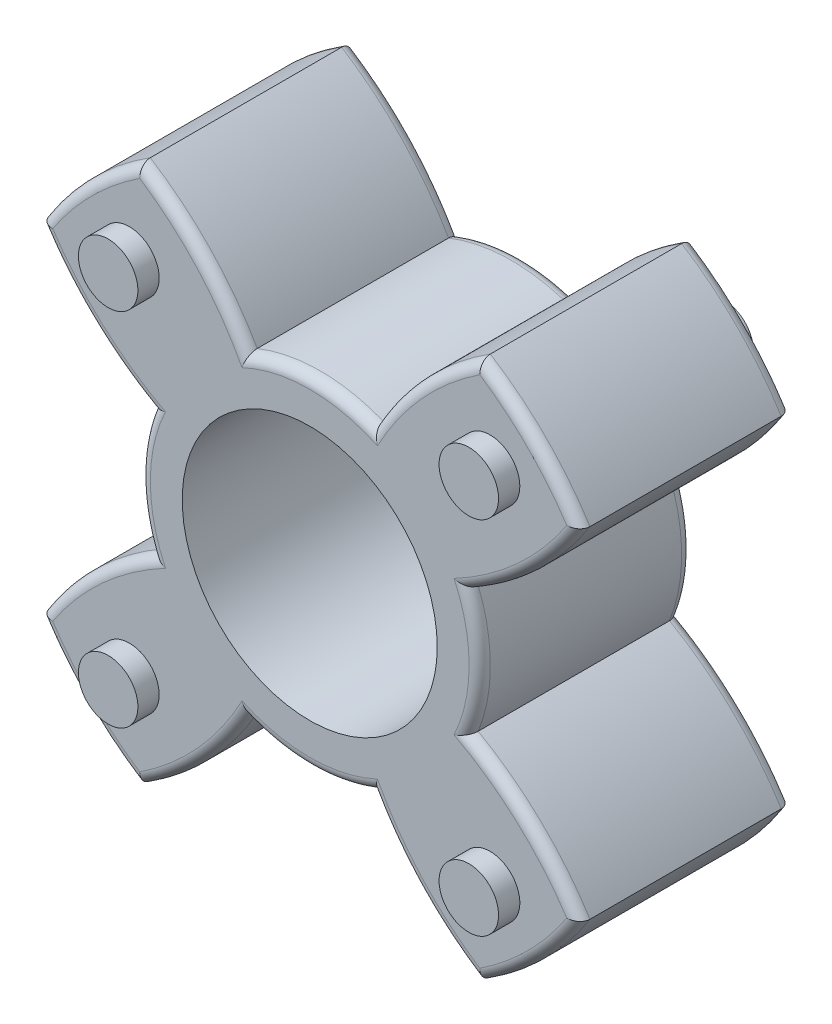
SolidWorks part; units mm, degrees
ref_plane "Front Plane" through (0, 0, 0) normal (0, 0, 1) x (1, 0, 0)
ref_plane "Top Plane" through (0, 0, 0) normal (0, 1, 0) x (1, 0, 0)
ref_plane "Right Plane" through (0, 0, 0) normal (1, 0, 0) x (0, 0, -1)
sketch "Sketch1" plane through (0, 0, 0) normal (0, 0, 1) x (1, 0, 0)
  arc A0 (8, 12.6886) -> (2.9688, 7.4288) centre (16, 0) ccw
  arc A1 (-8, -12.6886) -> (-2.9688, -7.4288) centre (-16, 0) ccw
  arc A2 (-12.6886, 8) -> (-7.4288, 2.9688) centre (0, 16) ccw
  arc A3 (12.6886, -8) -> (7.4288, -2.9688) centre (0, -16) ccw
  arc A4 (12.6886, 8) -> (8, 12.6886) centre (0, 0) ccw
  arc A5 (-8, 12.6886) -> (-12.6886, 8) centre (0, 0) ccw
  arc A6 (-12.6886, -8) -> (-8, -12.6886) centre (0, 0) ccw
  arc A7 (8, -12.6886) -> (12.6886, -8) centre (0, 0) ccw
  arc A8 (-7.4288, 2.9688) -> (-7.4288, -2.9688) centre (0, 0) ccw
  circle A9 centre (0, 0) radius 6
  arc A10 (7.4288, 2.9688) -> (12.6886, 8) centre (0, 16) ccw
  arc A11 (-2.9688, 7.4288) -> (-8, 12.6886) centre (-16, 0) ccw
  arc A12 (2.9688, 7.4288) -> (-2.9688, 7.4288) centre (0, 0) ccw
  arc A13 (-2.9688, -7.4288) -> (2.9687, -7.4288) centre (0, 0) ccw
  arc A14 (2.9687, -7.4288) -> (8, -12.6886) centre (16, 0) ccw
  arc A15 (7.4288, -2.9688) -> (7.4288, 2.9688) centre (0, 0) ccw
  arc A16 (-7.4288, -2.9688) -> (-12.6886, -8) centre (0, -16) ccw
extrude "Boss-Extrude1" add sketch "Sketch1" along normal blind 10
sketch "Sketch2" plane through (0, 0, 10) normal (0, 0, 1) x (1, 0, 0)
  circle A1 centre (-8.4853, 8.4853) radius 1.4
extrude "Boss-Extrude2" add sketch "Sketch2" along normal blind 1
ref_axis "Axis1" through (0, 0, 0) along (0, 0, 1)
pattern_circular "CirPattern1" count 4 over 360 about axis through (0, 0, 0) along (0, 0, 1) of "Boss-Extrude2"
sketch "Sketch3" plane through (0, 0, 0) normal (0, 0, -1) x (-1, 0, 0)
  circle A0 centre (-8.4853, 8.4853) radius 1.4
extrude "Boss-Extrude3" add sketch "Sketch3" along normal blind 1
pattern_circular "CirPattern2" count 2 over 360 about axis through (0, 0, 0) along (0, 0, 1) of "Boss-Extrude3"
fillet "Fillet1" radius 0.5 16 edges at (5.1605, -10.3685, 0) (0, -8, 0) (-5.1605, -10.3685, 0) (-10.6066, -10.6066, 0) (-10.3685, -5.1605, 0) (-8, 0, 0) (-10.3685, 5.1605, 0) (-10.6066, 10.6066, 0) (-5.1605, 10.3685, 0) (5.1605, 10.3685, 0) (10.6066, 10.6066, 0) (0, 8, 0) (10.3685, 5.1605, 0) (8, 0, 0) (10.3685, -5.1605, 0) (10.6066, -10.6066, 0)
fillet "Fillet2" radius 0.5 16 edges at (-10.3685, 5.1605, 10) (-8, 0, 10) (-10.3685, -5.1605, 10) (-10.6066, -10.6066, 10) (-5.1605, -10.3685, 10) (0, -8, 10) (5.1605, -10.3685, 10) (10.6066, -10.6066, 10) (10.3685, -5.1605, 10) (8, 0, 10) (10.3685, 5.1605, 10) (5.1605, 10.3685, 10) (10.6066, 10.6066, 10) (-5.1605, 10.3685, 10) (0, 8, 10) (-10.6066, 10.6066, 10)
